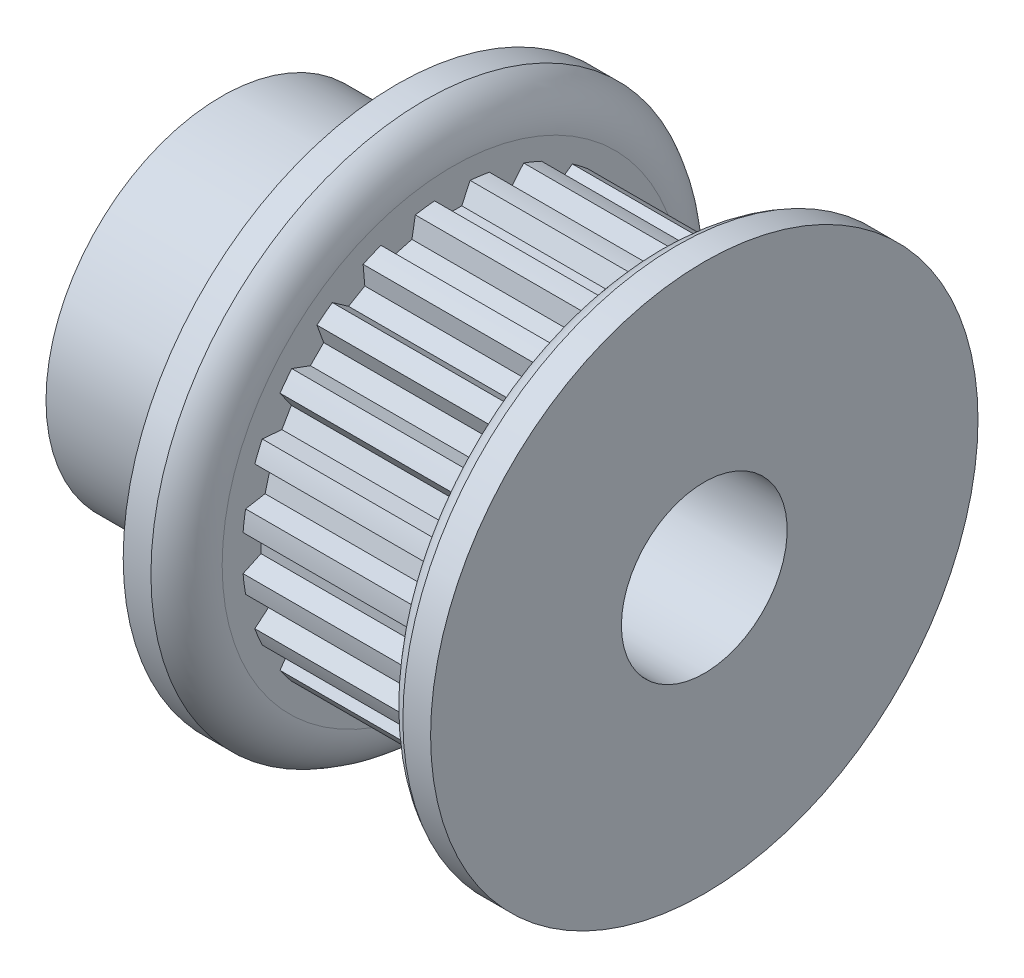
SolidWorks part; units mm, degrees
ref_plane "Front Plane" through (0, 0, 0) normal (0, 0, 1) x (1, 0, 0)
ref_plane "Top Plane" through (0, 0, 0) normal (0, 1, 0) x (1, 0, 0)
ref_plane "Right Plane" through (0, 0, 0) normal (1, 0, 0) x (0, 0, -1)
sketch "Sketch2" plane through (0, 0, 0) normal (1, 0, 0) x (0, 0, -1)
  line L3 (0, 0) -> (0, 6.9342) construction
  line L6 (0, -7.4422) -> (0, -7.7597) construction
  line L7 (-0.5715, 7.4202) -> (-0.341, 6.9258)
  line L8 (0.5715, 7.4202) -> (0.341, 6.9258)
  line L9 (-0.5715, 7.4202) -> (-0.6431, 7.5737)
  line L10 (0.5715, 7.4202) -> (0.6431, 7.5737)
  line L12 (-0.341, 6.9258) -> (0.341, 6.9258)
  line L14 (0, 7.4422) -> (0, 7.7597) construction
  line L15 (0, 0) -> (0, -1.143) construction
  circle A0 centre (0, 0) radius 7.7597 construction
  circle A1 centre (0, 0) radius 6.9342 construction
  circle A2 centre (0, 0) radius 7.4422 construction
  arc A7 (0.6431, 7.5737) -> (-0.6431, 7.5737) centre (0, 0) ccw
  point P5 (0, 7.6009)
  dimension "D3" = 0.3175
  dimension "D1" = 50
sketch "Sketch1" plane through (0, 0, 0) normal (0, 0, 1) x (1, 0, 0)
  line L0 (-8.7376, 0) -> (8.7376, 0) construction
  line L1 (-8.7376, 2.3813) -> (8.7376, 2.3813)
  line L2 (-8.7376, 2.3813) -> (-8.7376, 6.35)
  line L3 (-2.3876, 9.906) -> (-1.3843, 9.906)
  line L4 (-0.381, 7.7597) -> (-0.381, 8.3312)
  line L5 (-0.381, 8.9027) -> (-0.381, 7.7597) construction
  line L6 (-0.381, 7.7597) -> (6.731, 7.7597)
  line L7 (6.731, 7.7597) -> (6.731, 8.3312)
  line L8 (6.731, 7.7597) -> (8.7376, 7.7597) construction
  line L9 (7.7343, 9.906) -> (8.7376, 9.906)
  line L10 (8.7376, 9.906) -> (8.7376, 2.3813)
  line L11 (7.7343, 7.7597) -> (7.7343, 9.906) construction
  line L12 (-5.5626, 6.35) -> (-5.5626, 2.3812) construction
  line L13 (-2.3876, 9.906) -> (-2.3876, 6.35)
  line L14 (-2.3876, 6.35) -> (-8.7376, 6.35)
  arc A0 (6.731, 8.3312) -> (7.7343, 9.906) centre (8.4686, 8.3312) cw
  arc A1 (-0.381, 8.3312) -> (-1.3843, 9.906) centre (-2.1186, 8.3312) ccw
  dimension "Bore Size" = 4.7625
  dimension "Overall Width" = 17.4752
  dimension "Inside Width" = 7.112
  dimension "OD" = 19.812
  dimension "D2" = 15.5194
  dimension "D3" = 1.143
  dimension "D4" = 0.5715
  dimension "Outside Width" = 11.1252
revolve "Revolve1" add sketch "Sketch1" angle 360 mid plane about L0
sketch "Sketch4" plane through (-0.381, 0, 0) normal (1, 0, 0) x (0, 0, -1)
  circle A0 centre (0, 0) radius 7.601
  circle A2 centre (0, 0) radius 7.7597
  circle A3 centre (0, 0) radius 7.7597 construction
extrude "Cut-Extrude2" cut sketch "Sketch4" along normal up to surface (7.112 mm away) up to face at (6.731, 0, 7.7597)
sketch "Sketch3" plane through (-0.381, 0, 0) normal (1, 0, 0) x (0, 0, -1)
  line L2 (-0.5715, 7.4202) -> (-0.341, 6.9258) construction
  line L3 (-0.341, 6.9258) -> (0.341, 6.9258) construction
  line L4 (0.5715, 7.4202) -> (0.341, 6.9258) construction
  line L5 (-0.6431, 7.5737) -> (-0.341, 6.9258)
  line L6 (-0.341, 6.9258) -> (0.341, 6.9258)
  line L7 (0.6431, 7.5737) -> (0.341, 6.9258)
  arc A1 (0.6431, 7.5737) -> (-0.6431, 7.5737) centre (0, 0) ccw construction
  arc A2 (0.6431, 7.5737) -> (-0.6431, 7.5737) centre (0, 0) ccw
extrude "Cut-Extrude1" cut sketch "Sketch3" along normal up to surface (7.112 mm away) up to face at (6.731, 0, 8.3312)
pattern_circular "CirPattern1" count 24 over 360 of "Cut-Extrude1"
sketch "Sketch5" plane through (0, 0, 0) normal (0, 0, 1) x (1, 0, 0)
  line L1 (6.731, 8.3312) -> (6.731, -8.3312) construction
  point P0 (6.731, 0)
sketch "Sketch6" plane through (-8.7376, 0, 0) normal (-1, 0, 0) x (0, 0, 1)
  circle A0 centre (0, 0) radius 3
  dimension "D1" = 6
extrude "Cut-Extrude3" cut sketch "Sketch6" against normal through all
equation "\"D3@Sketch2\" = (\"hs@Sketch2\"-\"ht@Sketch2\")/2"
equation "\"D2@Sketch1\" = \"PD@Sketch2\""
equation "\"D3@Sketch1\" = \"hs@Sketch2\""
equation "\"D4@Sketch1\" = \"D3@Sketch1\"/2"
